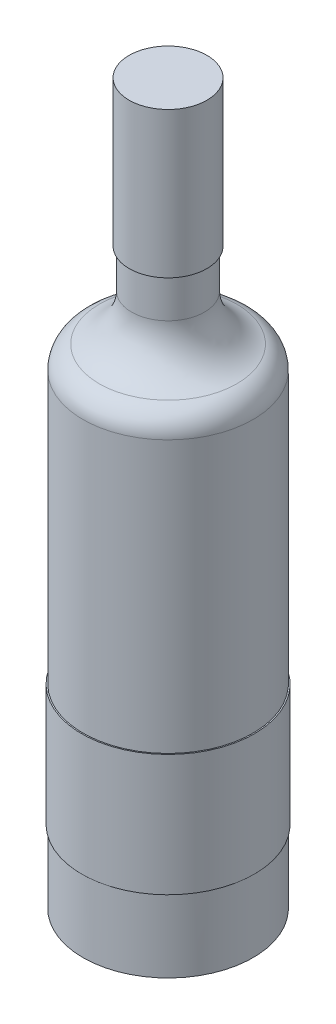
SolidWorks part; units mm, degrees
ref_plane "Front Plane" through (0, 0, 0) normal (0, 0, 1) x (1, 0, 0)
ref_plane "Top Plane" through (0, 0, 0) normal (0, 1, 0) x (1, 0, 0)
ref_plane "Right Plane" through (0, 0, 0) normal (1, 0, 0) x (0, 0, -1)
sketch "Sketch2" plane through (0, 0, 0) normal (0, 1, 0) x (1, 0, 0)
  circle A0 centre (0, 0) radius 35
  dimension "D1" = 70
extrude "Boss-Extrude1" add sketch "Sketch2" along normal blind 200
ref_axis "Axis1" through (0, 200, 0) along (0, -1, 0)
sketch "Sketch3" plane through (0, 200, 0) normal (0, 1, 0) x (1, 0, 0)
  circle A0 centre (0, 0) radius 15
  dimension "D1" = 30
extrude "Boss-Extrude2" add sketch "Sketch3" along normal blind 95
fillet "Fillet1" radius 20 1 edges at (0, 200, 15)
fillet "Fillet2" radius 10 1 edges at (0, 200, 35)
sketch "Sketch4" plane through (0, 295, 0) normal (0, 1, 0) x (1, 0, 0)
  circle A0 centre (0, 0) radius 16
  circle A1 centre (0, 0) radius 15 construction
  dimension "D1" = 1
extrude "Boss-Extrude3" add sketch "Sketch4" against normal blind 60 from offset 1
sketch "Sketch5" plane through (0, 0, 0) normal (0, -1, 0) x (1, 0, 0)
  circle A0 centre (0, 0) radius 35.5
  circle A1 centre (0, 0) radius 35 construction
  dimension "D1" = 0.5
extrude "Boss-Extrude4" add sketch "Sketch5" against normal blind 50 from offset 30 offset against normal yes
